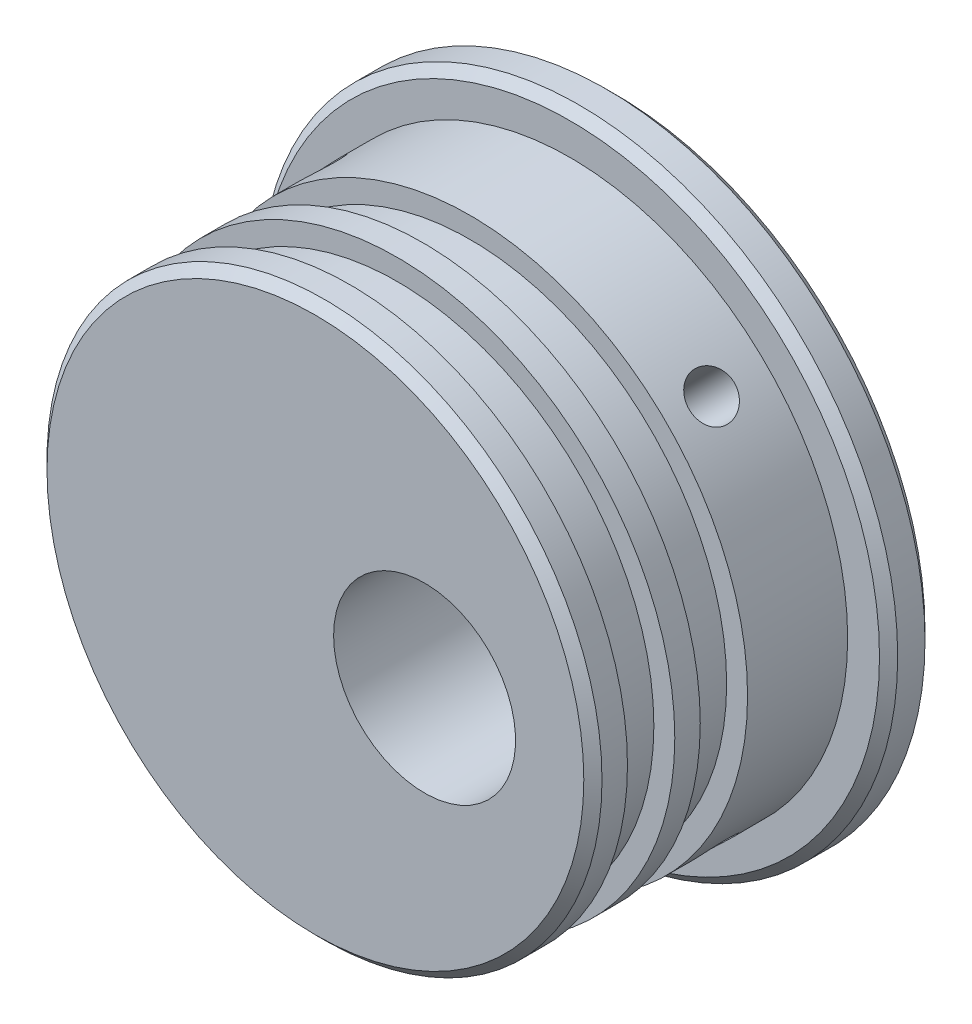
SolidWorks part; units mm, degrees
ref_plane "Спереди" through (0, 0, 0) normal (0, 0, 1) x (1, 0, 0)
ref_plane "Сверху" through (0, 0, 0) normal (0, 1, 0) x (1, 0, 0)
ref_plane "Справа" through (0, 0, 0) normal (1, 0, 0) x (0, 0, -1)
other "Configuration Table"
sketch "Эскиз1" plane through (0, 0, 0) normal (0, 0, 1) x (1, 0, 0)
  circle A0 centre (0, 0) radius 17.5
  circle A1 centre (0, 0) radius 15.25
  circle A2 centre (0, 0) radius 14.1
  dimension "D1" = 35
  dimension "D2" = 30.5
  dimension "D3" = 28.2
extrude "Бобышка-Вытянуть1" add sketch "Эскиз1" against normal blind 2.5 contours A0 A1 | A1 A2 | A2 region at (-17.005, 0, 0) region at (-14.8187, 0, 0) region at (0, 0, 0)
extrude "Бобышка-Вытянуть2" add sketch "Эскиз1<3>" along normal blind 14 contours A1 A2 | A2 region at (-14.8187, 0, 0) region at (0, 0, 0)
sketch "Эскиз1<3>" plane through (0, 0, 0) normal (0, 0, 1) x (1, 0, 0) same geometry as "Эскиз1"
extrude "Вырез-Вытянуть1" cut sketch "Эскиз1<4>" along normal blind 2.6 from offset 5.5 contours A1 A2 region at (-14.8187, 0, 0)
sketch "Эскиз1<4>" plane through (0, 0, 0) normal (0, 0, 1) x (1, 0, 0) same geometry as "Эскиз1"
extrude "Вырез-Вытянуть2" cut sketch "Эскиз1<5>" along normal blind 2.6 from offset 9.5 contours A1 A2 region at (-14.8187, 0, 0)
sketch "Эскиз1<5>" plane through (0, 0, 0) normal (0, 0, 1) x (1, 0, 0) same geometry as "Эскиз1"
chamfer "Фаска1" distance 0.5 angle 45 3 edges at (15.25, 0, 14) (17.5, 0, 0) (17.5, 0, -2.5)
sketch "Эскиз2" plane through (0, 0, -2.5) normal (0, 0, -1) x (-1, 0, 0)
  circle A0 centre (-6, 0) radius 5
  dimension "D1" = 10
  dimension "D2" = 6
sketch "Эскиз3" plane through (0, 0, 0) normal (0, 1, 0) x (1, 0, 0)
  line L0 (0, 0) -> (0, 5.0181)
ref_plane "Плоскость1" through (0, 0, 0) normal (0.7071, 0.7071, 0) x (0, 0, -1)
extrude "Вырез-Вытянуть5" cut sketch "Эскиз2" against normal through all
sketch "Эскиз4" plane through (0, 0, 0) normal (0.7071, 0.7071, 0) x (0, 0, -1)
  circle A0 centre (-3, 0) radius 1.25
  dimension "D1" = 2.5
  dimension "D2" = 3
extrude "Вырез-Вытянуть6" cut sketch "Эскиз4" along normal through all from offset 10
pattern_circular "Круговой массив1" count 4 every 90 about axis through (0, 0, 0) along (0, 0, -1) of "Вырез-Вытянуть6"
